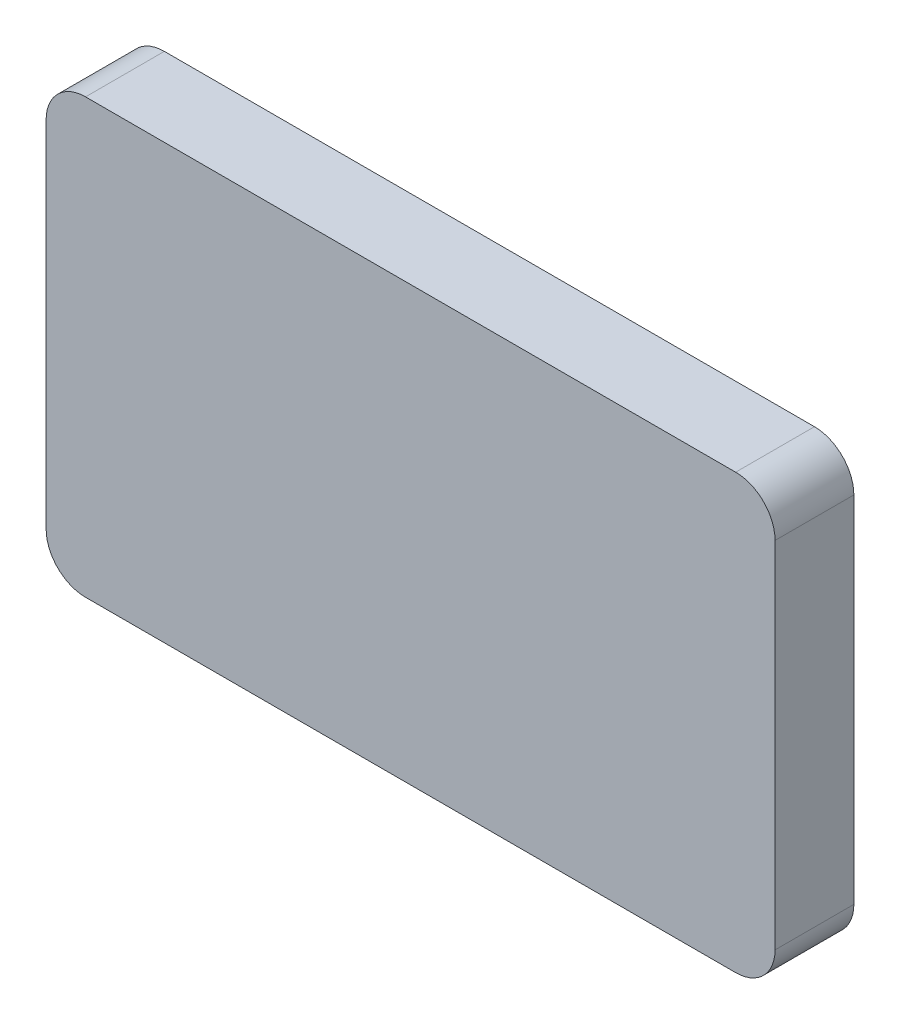
SolidWorks part; units mm, degrees
ref_plane "Front Plane" through (0, 0, 0) normal (0, 0, 1) x (1, 0, 0)
ref_plane "Top Plane" through (0, 0, 0) normal (0, 1, 0) x (1, 0, 0)
ref_plane "Right Plane" through (0, 0, 0) normal (1, 0, 0) x (0, 0, -1)
sketch "Sketch1" plane through (0, 0, 0) normal (0, 0, 1) x (1, 0, 0)
  line L1 (0, 0) -> (18.5, 0)
  line L2 (0, 0) -> (0, 11)
  line L3 (0, 11) -> (18.5, 11)
  line L4 (18.5, 0) -> (18.5, 11)
  line L5 (18.5, 7.25) -> (18.5, 4.9873)
  line L24 (18.5, 11) -> (-49981.5, 11) construction
  dimension "D1" = 11
  dimension "D2" = 18.5
extrude "Boss-Extrude2" add sketch "Sketch1" along normal blind 2 contours L1 L4 L3 L2 | L4 region at (9.25, 5.5, 0)
fillet "Fillet1" radius 1 4 edges at (0, 0, 1) (18.5, 0, 1) (18.5, 11, 1) (0, 11, 1)
